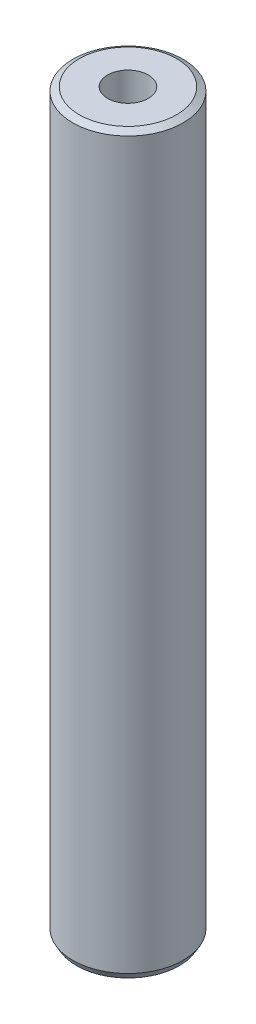
SolidWorks part; units mm, degrees
ref_plane "Front Plane" through (0, 0, 0) normal (0, 0, 1) x (1, 0, 0)
ref_plane "Top Plane" through (0, 0, 0) normal (0, 1, 0) x (1, 0, 0)
ref_plane "Right Plane" through (0, 0, 0) normal (1, 0, 0) x (0, 0, -1)
sketch "Sketch1" plane through (0, 0, 0) normal (0, 1, 0) x (1, 0, 0)
  circle A0 centre (0, 0) radius 45
  dimension "SHAFT_OD" = 90
extrude "Boss-Extrude1" add sketch "Sketch1" along normal blind 600
sketch "Sketch2" plane through (0, 0, 0) normal (0, 1, 0) x (1, 0, 0)
  circle A0 centre (0, 0) radius 16.6191
  dimension "BORE_D" = 33.2382
extrude "Cut-Extrude1" cut sketch "Sketch2" along normal through all
chamfer "Chamfer1" distance 3.0728 angle 60 2 edges at (0, 600, 45) (0, 0, 45) first distance on face at (0, 600, 45) first distance on face at (0, 0, 16.6191)
